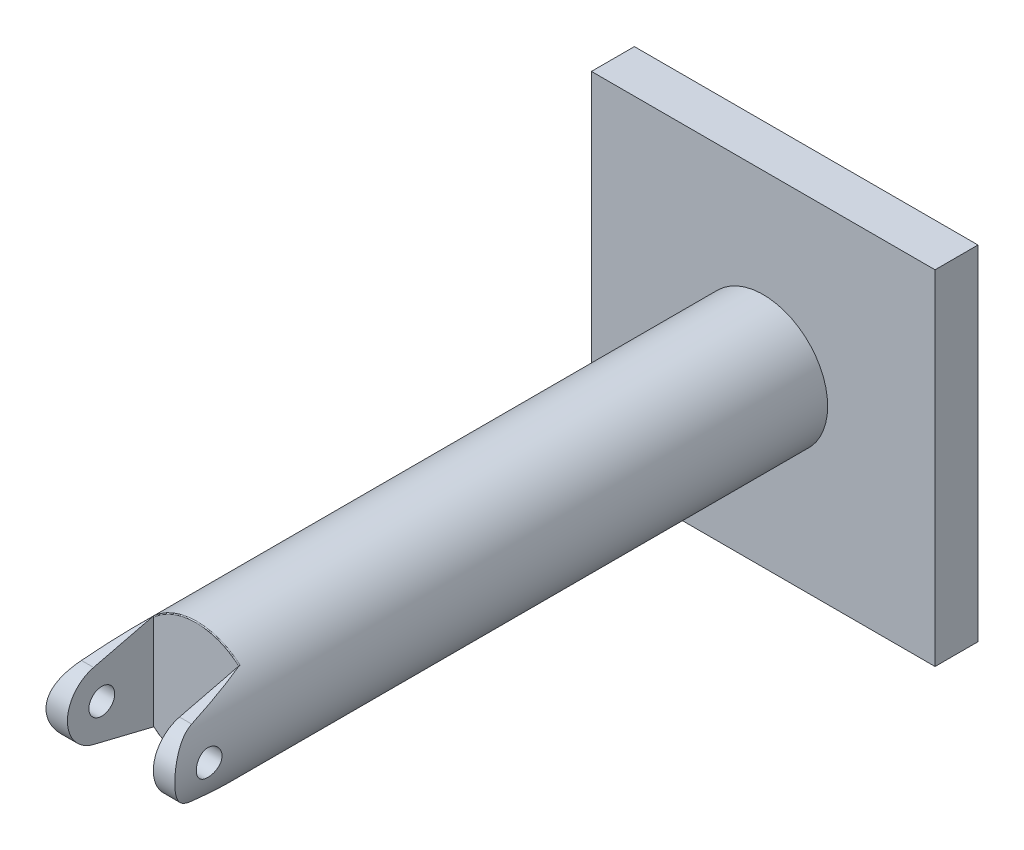
SolidWorks part; units mm, degrees
ref_plane "Ön Düzlem" through (0, 0, 0) normal (0, 0, 1) x (1, 0, 0)
ref_plane "Üst Düzlem" through (0, 0, 0) normal (0, 1, 0) x (1, 0, 0)
ref_plane "Sağ Düzlem" through (0, 0, 0) normal (1, 0, 0) x (0, 0, -1)
sketch "Sketch1" plane through (0, 0, 0) normal (0, 0, 1) x (1, 0, 0)
  circle A0 centre (0, 0) radius 7.5
  dimension "D1" = 15
extrude "Boss-Extrude1" add sketch "Sketch1" along normal blind 56
sketch "Sketch2" plane through (0, 0, 56) normal (0, 0, 1) x (1, 0, 0)
  line L1 (-5, 8) -> (5, 8)
  line L2 (-5, 8) -> (-5, -8)
  line L3 (-5, -8) -> (5, -8)
  line L4 (5, 8) -> (5, -8)
  dimension "D1" = 10
  dimension "D2" = 5
  dimension "D3" = 8
  dimension "D4" = 8
extrude "Cut-Extrude1" cut sketch "Sketch2" along direction (0, 0, 1) on the side against the normal blind 10
sketch "Sketch3" plane through (0, 0, 0) normal (1, 0, 0) x (0, 0, -1)
  line L0 (-46, -7.5) -> (-46, -5.5902)
  line L1 (-46, 7.5) -> (-46, 5.5902)
  line L2 (-46, 5.5902) -> (-52.9529, 3.8847)
  line L3 (-46, -5.5902) -> (-52.9527, -3.885)
  line L4 (-56, -5.5902) -> (-46, -5.5902) construction
  line L5 (-56, 5.5902) -> (-56, -5.5902) construction
  arc A0 (-52.9529, 3.8847) -> (-52.9527, -3.885) centre (-52, -0.0002) ccw
  dimension "D1" = 4
  dimension "D2" = 5.59
extrude "Cut-Extrude4" cut sketch "Sketch3" against normal through all and the other way through all flip side to cut
sketch "Sketch4" plane through (0, 0, 0) normal (1, 0, 0) x (0, 0, -1)
  circle A0 centre (-52, -0.0002) radius 1.5
  arc A1 (-52.9529, 3.8847) -> (-52.9527, -3.885) centre (-52, -0.0002) ccw construction
  dimension "D1" = 3
extrude "Cut-Extrude5" cut sketch "Sketch4" against normal through all and the other way through all
fillet "Fillet1" radius 0.1 2 edges at (0, 7.5, 46) (0, -7.5, 46)
sketch "Sketch5" plane through (0, 0, 0) normal (0, 1, 0) x (1, 0, 0)
  line L0 (0, 0) -> (0, 20)
  line L1 (-7.5, 0) -> (-7.5, 20)
  line L2 (-7.5, 0) -> (0, 0)
  line L3 (0, 20) -> (-7.5, 20)
  dimension "D1" = 20
revolve "Revolve1" add sketch "Sketch5" angle 360 about L0
sketch "Sketch6" plane through (0, 0, -20) normal (0, 0, -1) x (-1, 0, 0)
  line L1 (20, 20) -> (-20, 20)
  line L2 (20, 20) -> (20, -20)
  line L3 (20, -20) -> (-20, -20)
  line L4 (-20, 20) -> (-20, -20)
  line L5 (20, 20) -> (-20, -20) construction
  line L6 (20, -20) -> (-20, 20) construction
  point P0 (0, 0)
  dimension "D1" = 40
  dimension "D2" = 40
extrude "Boss-Extrude2" add sketch "Sketch6" along normal blind 5
